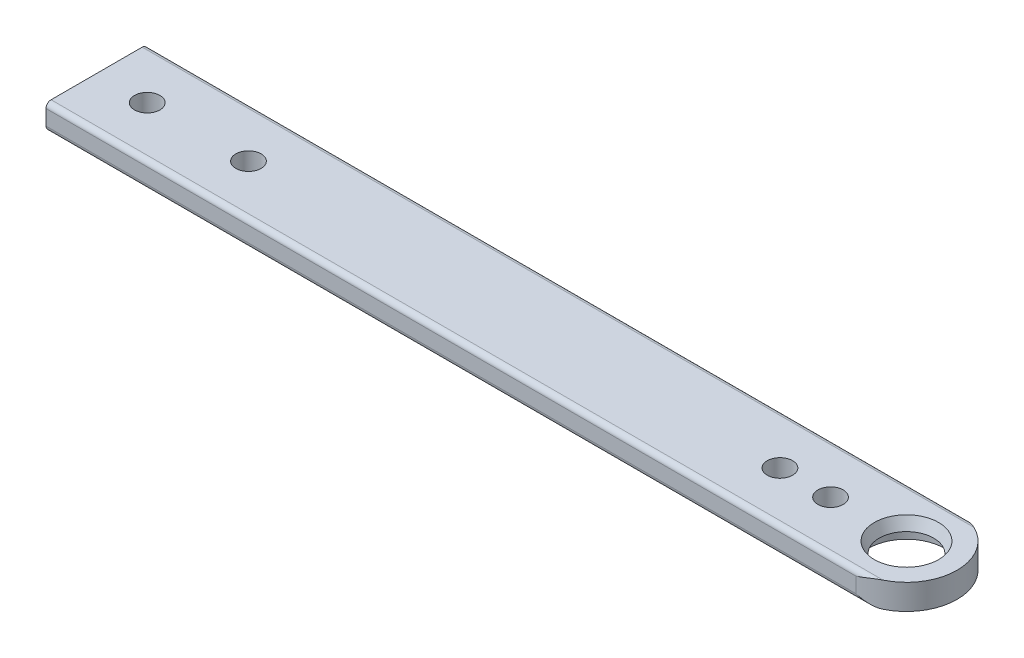
SolidWorks part; units mm, degrees
material "Plain Carbon Steel"
ref_plane "Front Plane" through (0, 0, 0) normal (0, 0, 1) x (1, 0, 0)
ref_plane "Top Plane" through (0, 0, 0) normal (0, 1, 0) x (1, 0, 0)
ref_plane "Right Plane" through (0, 0, 0) normal (1, 0, 0) x (0, 0, -1)
sketch "Sketch1" plane through (0, 0, 0) normal (0, 1, 0) x (1, 0, 0)
  line L1 (107.95, -12.7) -> (-107.95, -12.7)
  line L2 (107.95, -12.7) -> (107.95, 12.7)
  line L3 (107.95, 12.7) -> (-107.95, 12.7)
  line L4 (-107.95, -12.7) -> (-107.95, 12.7)
  line L5 (107.95, -12.7) -> (-107.95, 12.7) construction
  line L6 (107.95, 12.7) -> (-107.95, -12.7) construction
  point P0 (0, 0)
  dimension "D1" = 25.4
  dimension "D2" = 215.9
extrude "Boss-Extrude1" add sketch "Sketch1" along normal blind 6.35
fillet "Fillet1" radius 1.27 4 edges at (0, 0, -12.7) (0, 6.35, -12.7) (0, 0, 12.7) (0, 6.35, 12.7)
sketch "Sketch2" plane through (0, 6.35, 0) normal (0, 1, 0) x (1, 0, 0)
  line L0 (-107.95, 0) -> (107.95, 0) construction
  line L1 (-107.95, 11.43) -> (-107.95, -11.43) construction
  line L2 (107.95, -11.43) -> (107.95, 11.43) construction
  circle A0 centre (-95.25, 0) radius 3.175
  circle A3 centre (95.25, 0) radius 6.35
  circle A7 centre (-69.85, 0) radius 3.175
  line M13 (107.95, 11.43) -> (-107.95, 11.43)
  line M15 (-107.95, -11.43) -> (107.95, -11.43)
  dimension "D1" = 12.7
  dimension "D4" = 6.35
  dimension "D2" = 190.5
  dimension "D3" = 12.7
  dimension "D5" = 2
extrude "Cut-Extrude1" cut sketch "Sketch2" against normal through all contours M13 | M15 | A0 L0 | L0 A3 | A3 L0 | A0 | A7 region at (-95.25, 6.35, -1.3475) region at (95.25, 6.35, -2.695) region at (95.25, 6.35, 2.695)
sketch "Sketch3" plane through (0, 0, 0) normal (0, -1, 0) x (1, 0, 0)
  circle A0 centre (95.25, 0) radius 9.525
  dimension "D1" = 19.05
extrude "Cut-Extrude2" cut sketch "Sketch3" against normal blind 3.5719
sketch "Sketch4" plane through (0, 0, 0) normal (0, -1, 0) x (1, 0, 0)
  line L1 (82.55, -12.7) -> (107.95, -12.7)
  line L2 (82.55, -12.7) -> (82.55, 12.7)
  line L3 (82.55, 12.7) -> (107.95, 12.7)
  line L4 (107.95, -12.7) -> (107.95, 12.7)
  line L5 (82.55, -12.7) -> (107.95, 12.7) construction
  line L6 (82.55, 12.7) -> (107.95, -12.7) construction
  circle A0 centre (95.25, 0) radius 12.7
  point P0 (95.25, 0)
  line M9 (-107.95, -11.43) -> (107.95, -11.43)
  line M10 (107.95, -11.43) -> (107.95, 11.43)
  line M11 (107.95, 11.43) -> (-107.95, 11.43)
extrude "Cut-Extrude3" cut sketch "Sketch4" against normal through all contours A0 L4 L3 M11 | A0 L4 M11 | A0 M9 M10 | A0 L1 L4 M9 region at (103.3706, 0, -12.1169) region at (105.9682, 0, -8.7575) region at (105.9682, 0, 8.7575) region at (103.3706, 0, 12.1169)
sketch "Sketch5" plane through (0, 0, 0) normal (0, -1, 0) x (1, 0, 0)
  line L0 (-107.95, 0) -> (107.95, 0) construction
  circle A0 centre (76.2, 0) radius 3.175
  circle A1 centre (63.5, 0) radius 3.175
  dimension "D1" = 6.35
  dimension "D2" = 12.7
  dimension "D3" = 19.05
extrude "Cut-Extrude4" cut sketch "Sketch5" against normal through all
ref_axis "Axis1" through (95.25, 3.5719, 0) along (0, 1, 0)
ref_plane "Plane2" through (0, 0, 0) normal (0, 0, 1) x (1, 0, 0)
sketch "Sketch8" plane through (0, 0, 0) normal (0, 0, 1) x (1, 0, 0)
  line L1 (95.25, 6.35) -> (95.25, 0)
  line L3 (95.25, 3.5719) -> (95.25, 6.35) construction
  line L12 (-107.95, 6.35) -> (100.7858, 6.35) construction
  line L13 (100.7858, 0) -> (-107.95, 0) construction
  line L14 (95.25, 0) -> (98.9442, 8.2974)
  line L15 (98.9442, 8.2974) -> (103.3182, 6.35)
  line L16 (103.3182, 6.35) -> (99.624, -1.9474)
  line L17 (99.624, -1.9474) -> (95.25, 0)
  line L18 (107.95, 6.35) -> (100.7858, 6.35) construction
  line L19 (95.25, 6.35) -> (101.6, 6.35)
  line L36 (101.6, 6.35) -> (101.6, 3.5719)
  line L37 (101.6, 3.5719) -> (95.25, 3.5719)
  line L38 (101.6, 6.35) -> (103.3182, 6.35)
  line L39 (101.6, 3.5719) -> (102.0813, 3.5719)
  dimension "D1" = 24
  dimension "D2" = 4.7879
  dimension "D3" = 6.35
  dimension "D4" = 2.7781
revolve "Cut-Revolve1" cut sketch "Sketch8" angle 360 about axis through (95.25, 3.5719, 0) along (0, 1, 0) region at (102.2078, 5.2213, 0)
